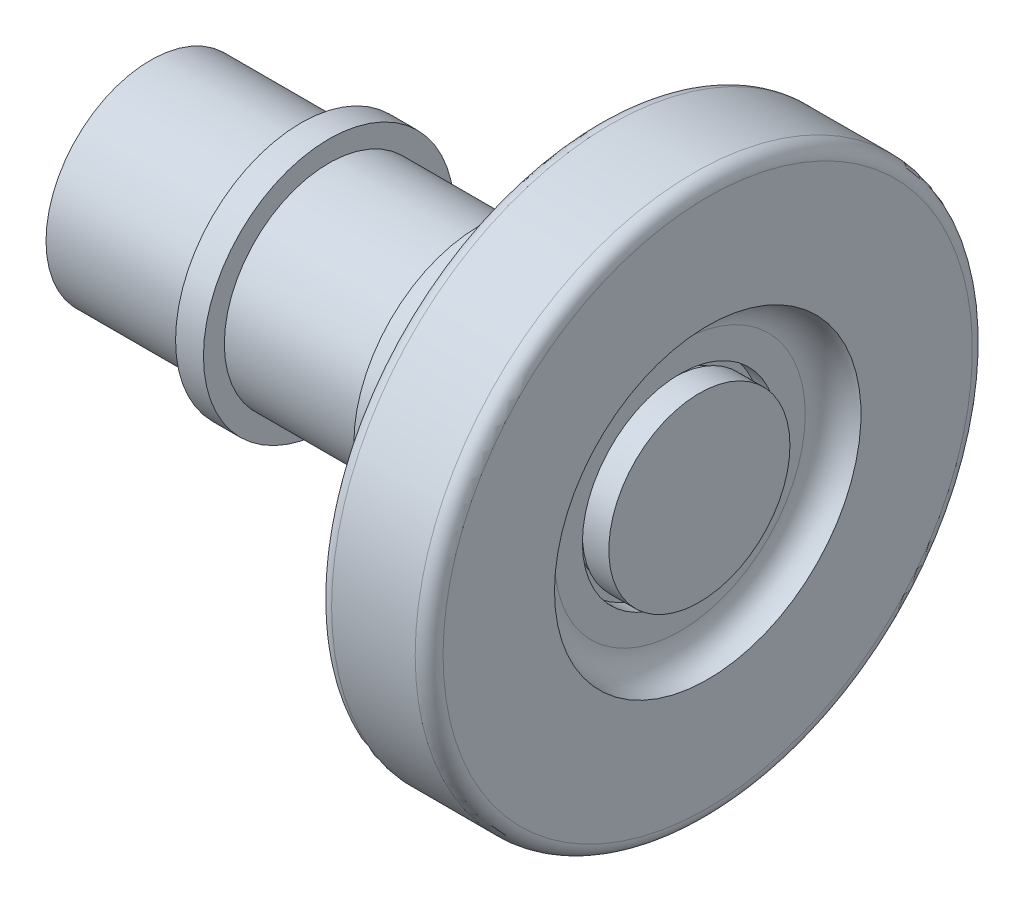
SolidWorks part; units mm, degrees
ref_plane "前视基准面" through (0, 0, 0) normal (0, 0, 1) x (1, 0, 0)
ref_plane "上视基准面" through (0, 0, 0) normal (0, 1, 0) x (1, 0, 0)
ref_plane "右视基准面" through (0, 0, 0) normal (1, 0, 0) x (0, 0, -1)
sketch "草图1" plane through (0, 0, 0) normal (0, 0, 1) x (1, 0, 0)
  line L0 (10, 100) -> (50, 100)
  line L1 (50, 100) -> (50, 55)
  line L2 (50, 55) -> (40, 55)
  line L3 (40, 55) -> (40, 35)
  line L6 (40, 35) -> (0, 35)
  line L7 (0, 35) -> (0, 70)
  line L8 (0, 70) -> (10, 70)
  line L9 (10, 70) -> (10, 100)
  line L10 (-1000, 0) -> (49000, 0) construction
  dimension "D1" = 35
  dimension "D2" = 70
  dimension "D3" = 10
  dimension "D4" = 40
  dimension "D5" = 100
  dimension "D6" = 55
  dimension "D7" = 10
revolve "旋转1" add sketch "草图1" angle 360 about L10
fillet "圆角1" radius 5 3 edges at (50, 0, 100) (10, 0, 100) (10, 0, 70)
fillet "圆角2" radius 10 1 edges at (40, 0, 55)
sketch "草图2" plane through (0, 0, 0) normal (-1, 0, 0) x (0, 0, 1)
  circle A0 centre (0, 0) radius 35
  circle A1 centre (0, 0) radius 35 construction
  circle A2 centre (0, 0) radius 45
  dimension "D1" = 90
extrude "凸台-拉伸1" add sketch "草图2" along normal blind 32 separate body
sketch "草图3" plane through (-32, 0, 0) normal (-1, 0, 0) x (0, 0, 1)
  circle A0 centre (0, 0) radius 35
  circle A1 centre (0, 0) radius 35 construction
extrude "凸台-拉伸2" add sketch "草图3" against normal blind 66
sketch "草图4" plane through (-32, 0, 0) normal (-1, 0, 0) x (0, 0, 1)
  circle A0 centre (0, 0) radius 37.5
  circle A1 centre (0, 0) radius 45 construction
  dimension "D1" = 75
extrude "凸台-拉伸3" add sketch "草图4" along normal blind 54
sketch "草图5" plane through (-86, 0, 0) normal (-1, 0, 0) x (0, 0, 1)
  circle A0 centre (0, 0) radius 45
  circle A1 centre (0, 0) radius 37.5 construction
  dimension "D1" = 90
extrude "凸台-拉伸4" add sketch "草图5" along normal blind 10
sketch "草图6" plane through (-96, 0, 0) normal (-1, 0, 0) x (0, 0, 1)
  circle A0 centre (0, 0) radius 37.5
  circle A1 centre (0, 0) radius 45 construction
  dimension "D1" = 75
extrude "凸台-拉伸5" add sketch "草图6" along normal blind 54
sketch "草图9" plane through (34, 0, 0) normal (1, 0, 0) x (0, 0, -1)
  circle A0 centre (0, 0) radius 31
  circle A1 centre (0, 0) radius 35 construction
  dimension "D1" = 62
extrude "凸台-拉伸8" add sketch "草图9" along normal blind 3.5
sketch "草图10" plane through (37.5, 0, 0) normal (1, 0, 0) x (0, 0, -1)
  circle A0 centre (0, 0) radius 32.5
  circle A1 centre (0, 0) radius 31 construction
  dimension "D1" = 65
extrude "凸台-拉伸9" add sketch "草图10" along normal blind 9.5
